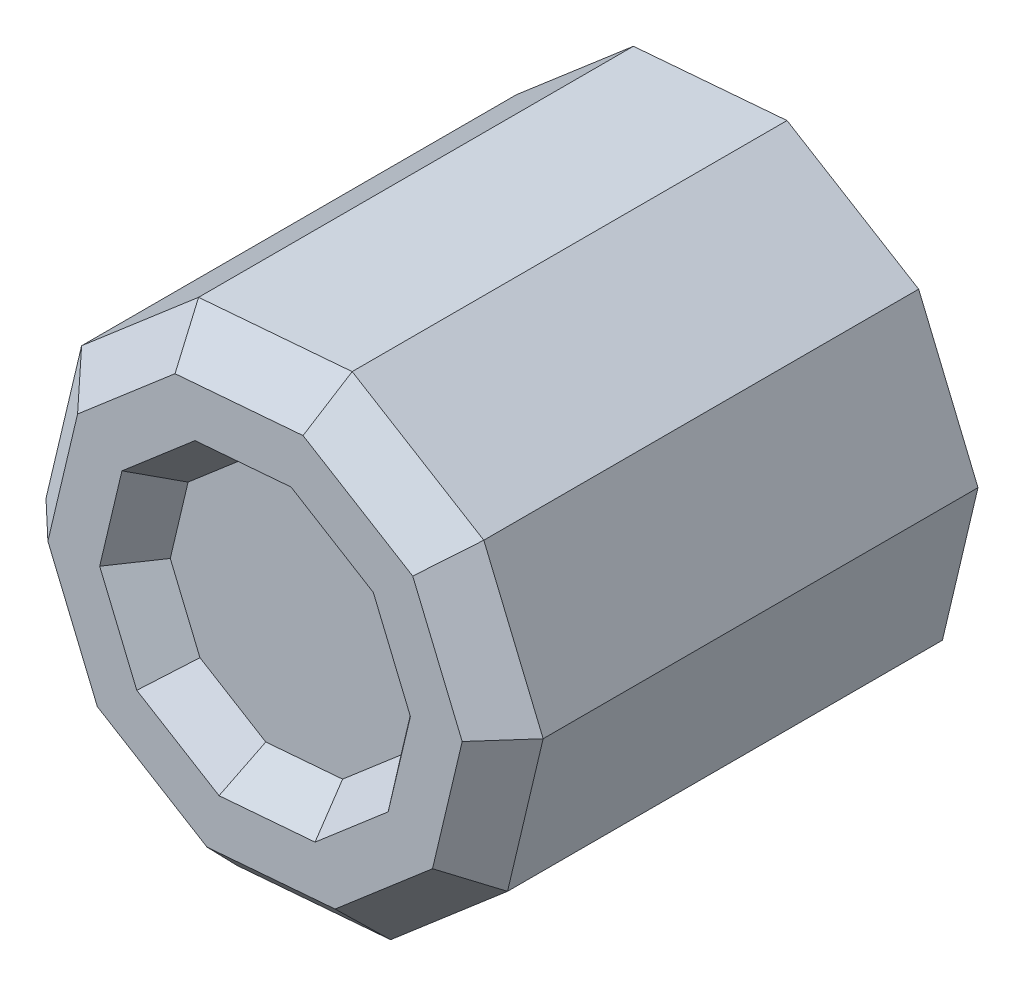
SolidWorks part; units mm, degrees
ref_plane "前视基准面" through (0, 0, 0) normal (0, 0, 1) x (1, 0, 0)
ref_plane "上视基准面" through (0, 0, 0) normal (0, 1, 0) x (1, 0, 0)
ref_plane "右视基准面" through (0, 0, 0) normal (1, 0, 0) x (0, 0, -1)
other "Configuration Table"
sketch "草图1" plane through (0, 0, 0) normal (0, 0, 1) x (1, 0, 0)
  line L1 (1.4571, 6.1382) -> (-2.4291, 5.8224)
  line L2 (-2.4291, 5.8224) -> (-5.3875, 3.2826)
  line L3 (-5.3875, 3.2826) -> (-6.288, -0.511)
  line L4 (-6.288, -0.511) -> (-4.7868, -4.1094)
  line L5 (-4.7868, -4.1094) -> (-1.4571, -6.1382)
  line L6 (-1.4571, -6.1382) -> (2.4291, -5.8224)
  line L7 (2.4291, -5.8224) -> (5.3875, -3.2826)
  line L8 (5.3875, -3.2826) -> (6.288, 0.511)
  line L9 (6.288, 0.511) -> (4.7868, 4.1094)
  line L10 (4.7868, 4.1094) -> (1.4571, 6.1382)
  circle A0 centre (0, 0) radius 3.05
  circle A1 centre (0, 0) radius 6 construction
  dimension "D1" = 6.1
  dimension "D2" = 12
extrude "凸台-拉伸1" add sketch "草图1" along normal blind 12
sketch "草图2" plane through (0, 0, 12) normal (0, 0, 1) x (1, 0, 0)
  circle A0 centre (0, 0) radius 3.0982
extrude "凸台-拉伸2" add sketch "草图2" against normal blind 2
sketch "草图3" plane through (0, 0, 10) normal (0, 0, -1) x (-1, 0, 0)
  line L1 (1.45, 2.6833) -> (1.45, -2.6833)
  circle A1 centre (0, 0) radius 3.05 construction
  circle A2 centre (0, 0) radius 3.05 construction
  arc A3 (1.45, -2.6833) -> (1.45, 2.6833) centre (0, 0) ccw
  point P1 (-3.05, 0)
  dimension "D1" = 4.5
extrude "凸台-拉伸3" add sketch "草图3" along normal blind 7
chamfer "倒角1" distance 1 angle 45 10 edges at (5.5374, 2.3102, 12) (5.8378, -1.3858, 12) (3.9083, -4.5525, 12) (0.486, -5.9803, 12) (-3.122, -5.1238, 12) (-5.5374, -2.3102, 12) (-5.8378, 1.3858, 12) (-3.9083, 4.5525, 12) (-0.486, 5.9803, 12) (3.122, 5.1238, 12)
ref_plane "基准面1" through (0, 0, 11) normal (0, 0, 1) x (1, 0, 0)
sketch "草图4" plane through (0, 0, 11) normal (0, 0, 1) x (1, 0, 0)
  line L0 (1.4571, 6.1382) -> (-1.4571, -6.1382) construction
  line L1 (0.7286, 3.0691) -> (-1.2145, 2.9112)
  line L2 (-1.2145, 2.9112) -> (-2.6937, 1.6413)
  line L3 (-2.6937, 1.6413) -> (-3.144, -0.2555)
  line L4 (-3.144, -0.2555) -> (-2.3934, -2.0547)
  line L5 (-2.3934, -2.0547) -> (-0.7286, -3.0691)
  line L6 (-0.7286, -3.0691) -> (1.2145, -2.9112)
  line L7 (1.2145, -2.9112) -> (2.6937, -1.6413)
  line L8 (2.6937, -1.6413) -> (3.144, 0.2555)
  line L9 (3.144, 0.2555) -> (2.3934, 2.0547)
  line L10 (2.3934, 2.0547) -> (0.7286, 3.0691)
  circle A0 centre (0, 0) radius 3 construction
  dimension "D1" = 6
sketch "草图5" plane through (0, 0, 12) normal (0, 0, 1) x (1, 0, 0)
  line L1 (0.9107, 3.8364) -> (-1.5182, 3.639)
  line L2 (-1.5182, 3.639) -> (-3.3672, 2.0516)
  line L3 (-3.3672, 2.0516) -> (-3.93, -0.3194)
  line L4 (-3.93, -0.3194) -> (-2.9917, -2.5684)
  line L5 (-2.9917, -2.5684) -> (-0.9107, -3.8364)
  line L6 (-0.9107, -3.8364) -> (1.5182, -3.639)
  line L7 (1.5182, -3.639) -> (3.3672, -2.0516)
  line L8 (3.3672, -2.0516) -> (3.93, 0.3194)
  line L9 (3.93, 0.3194) -> (2.9917, 2.5684)
  line L10 (2.9917, 2.5684) -> (0.9107, 3.8364)
  circle A0 centre (0, 0) radius 3.75 construction
loft "切除-放样1" cut profiles "草图5", "草图4" connector at (-1.5182, 3.639, 12) connector at (-1.2145, 2.9112, 11)
